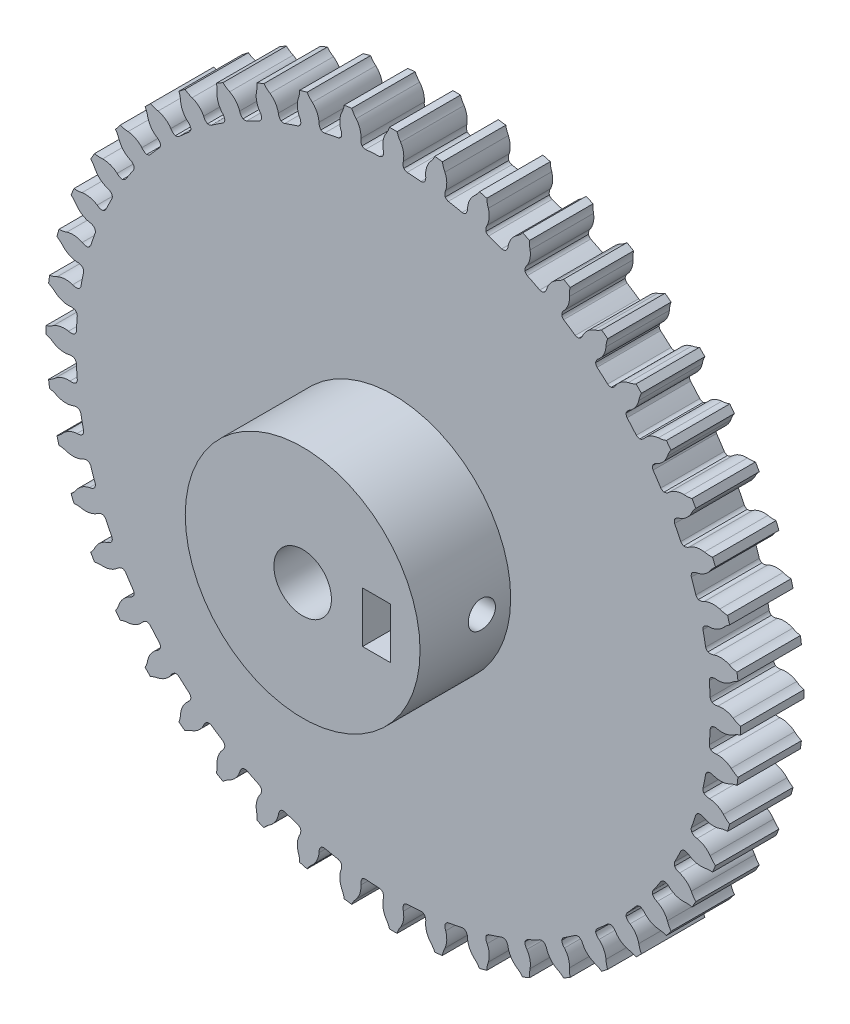
SolidWorks part; units mm, degrees
ref_plane "Front Plane" through (0, 0, 0) normal (0, 0, 1) x (1, 0, 0)
ref_plane "Top Plane" through (0, 0, 0) normal (0, 1, 0) x (1, 0, 0)
ref_plane "Right Plane" through (0, 0, 0) normal (1, 0, 0) x (0, 0, -1)
sketch "Sketch1" plane through (0, 0, 0) normal (0, 0, 1) x (1, 0, 0)
  line L0 (27.683, 56.4388) -> (28.5235, 56.4388)
  line L1 (28.5235, 56.4388) -> (28.1033, 56.4388)
  line L2 (32.6869, 56.1659) -> (33.5201, 56.0562)
  line L3 (33.5201, 56.0562) -> (33.1035, 56.1111)
  line L4 (37.6123, 55.2422) -> (38.4241, 55.0247)
  line L5 (38.4241, 55.0247) -> (38.0182, 55.1335)
  line L6 (42.375, 53.6836) -> (43.1514, 53.3619)
  line L7 (43.1514, 53.3619) -> (42.7632, 53.5227)
  line L8 (46.8935, 51.5166) -> (47.6213, 51.0964)
  line L9 (47.6213, 51.0964) -> (47.2574, 51.3065)
  line L10 (51.0905, 48.7783) -> (51.7572, 48.2667)
  line L11 (51.7572, 48.2667) -> (51.4239, 48.5225)
  line L12 (54.8942, 45.5157) -> (55.4884, 44.9214)
  line L13 (55.4884, 44.9214) -> (55.1913, 45.2186)
  line L14 (58.2394, 41.7845) -> (58.7511, 41.1177)
  line L15 (58.7511, 41.1177) -> (58.4953, 41.4511)
  line L16 (61.0691, 37.6486) -> (61.4893, 36.9207)
  line L17 (61.4893, 36.9207) -> (61.2792, 37.2847)
  line L18 (63.3347, 33.1787) -> (63.6563, 32.4022)
  line L19 (63.6563, 32.4022) -> (63.4955, 32.7905)
  line L20 (64.9974, 28.4513) -> (65.215, 27.6395)
  line L21 (65.215, 27.6395) -> (65.1062, 28.0454)
  line L22 (66.0289, 23.5474) -> (66.1386, 22.7141)
  line L23 (66.1386, 22.7141) -> (66.0838, 23.1308)
  line L24 (66.4115, 18.5507) -> (66.4115, 17.7103)
  line L25 (66.4115, 17.7103) -> (66.4115, 18.1305)
  line L26 (66.1386, 13.5469) -> (66.0289, 12.7137)
  line L27 (66.0289, 12.7137) -> (66.0838, 13.1303)
  line L28 (65.215, 8.6215) -> (64.9974, 7.8097)
  line L29 (64.9974, 7.8097) -> (65.1062, 8.2156)
  line L30 (63.6563, 3.8588) -> (63.3347, 3.0824)
  line L31 (63.3347, 3.0824) -> (63.4955, 3.4706)
  line L32 (61.4893, -0.6597) -> (61.0691, -1.3875)
  line L33 (61.0691, -1.3875) -> (61.2792, -1.0236)
  line L34 (58.7511, -4.8567) -> (58.2394, -5.5235)
  line L35 (58.2394, -5.5235) -> (58.4953, -5.1901)
  line L36 (55.4884, -8.6604) -> (54.8942, -9.2546)
  line L37 (54.8942, -9.2546) -> (55.1913, -8.9575)
  line L38 (51.7572, -12.0057) -> (51.0905, -12.5173)
  line L39 (51.0905, -12.5173) -> (51.4239, -12.2615)
  line L40 (47.6213, -14.8353) -> (46.8935, -15.2555)
  line L41 (46.8935, -15.2555) -> (47.2574, -15.0454)
  line L42 (43.1514, -17.1009) -> (42.375, -17.4225)
  line L43 (42.375, -17.4225) -> (42.7632, -17.2617)
  line L44 (38.4241, -18.7637) -> (37.6123, -18.9812)
  line L45 (37.6123, -18.9812) -> (38.0182, -18.8724)
  line L46 (33.5201, -19.7952) -> (32.6869, -19.9049)
  line L47 (32.6869, -19.9049) -> (33.1035, -19.85)
  line L48 (28.5235, -20.1777) -> (27.683, -20.1777)
  line L49 (27.683, -20.1777) -> (28.1033, -20.1777)
  line L50 (23.5196, -19.9049) -> (22.6864, -19.7952)
  line L51 (22.6864, -19.7952) -> (23.103, -19.85)
  line L52 (18.5942, -18.9812) -> (17.7825, -18.7637)
  line L53 (17.7825, -18.7637) -> (18.1883, -18.8724)
  line L54 (13.8315, -17.4225) -> (13.0551, -17.1009)
  line L55 (13.0551, -17.1009) -> (13.4433, -17.2617)
  line L56 (9.313, -15.2555) -> (8.5852, -14.8353)
  line L57 (8.5852, -14.8353) -> (8.9491, -15.0454)
  line L58 (5.116, -12.5173) -> (4.4493, -12.0057)
  line L59 (4.4493, -12.0057) -> (4.7827, -12.2615)
  line L60 (1.3124, -9.2546) -> (0.7181, -8.6604)
  line L61 (0.7181, -8.6604) -> (1.0152, -8.9575)
  line L62 (-2.0329, -5.5235) -> (-2.5445, -4.8567)
  line L63 (-2.5445, -4.8567) -> (-2.2887, -5.1901)
  line L64 (-4.8626, -1.3875) -> (-5.2828, -0.6597)
  line L65 (-5.2828, -0.6597) -> (-5.0727, -1.0236)
  line L66 (-7.1282, 3.0824) -> (-7.4498, 3.8588)
  line L67 (-7.4498, 3.8588) -> (-7.289, 3.4706)
  line L68 (-8.7909, 7.8097) -> (-9.0084, 8.6215)
  line L69 (-9.0084, 8.6215) -> (-8.8997, 8.2156)
  line L70 (-9.8224, 12.7137) -> (-9.9321, 13.5469)
  line L71 (-9.9321, 13.5469) -> (-9.8773, 13.1303)
  line L72 (-10.205, 17.7103) -> (-10.205, 18.5507)
  line L73 (-10.205, 18.5507) -> (-10.205, 18.1305)
  line L74 (-9.9321, 22.7141) -> (-9.8224, 23.5474)
  line L75 (-9.8224, 23.5474) -> (-9.8773, 23.1308)
  line L76 (-9.0084, 27.6395) -> (-8.7909, 28.4513)
  line L77 (-8.7909, 28.4513) -> (-8.8997, 28.0454)
  line L78 (-7.4498, 32.4022) -> (-7.1282, 33.1787)
  line L79 (-7.1282, 33.1787) -> (-7.289, 32.7905)
  line L80 (-5.2828, 36.9207) -> (-4.8626, 37.6486)
  line L81 (-4.8626, 37.6486) -> (-5.0727, 37.2847)
  line L82 (-2.5445, 41.1177) -> (-2.0329, 41.7845)
  line L83 (-2.0329, 41.7845) -> (-2.2887, 41.4511)
  line L84 (0.7181, 44.9214) -> (1.3124, 45.5157)
  line L85 (1.3124, 45.5157) -> (1.0152, 45.2186)
  line L86 (4.4493, 48.2667) -> (5.116, 48.7783)
  line L87 (5.116, 48.7783) -> (4.7827, 48.5225)
  line L88 (8.5852, 51.0964) -> (9.313, 51.5166)
  line L89 (9.313, 51.5166) -> (8.9491, 51.3065)
  line L90 (13.0551, 53.3619) -> (13.8315, 53.6836)
  line L91 (13.8315, 53.6836) -> (13.4433, 53.5227)
  line L92 (17.7825, 55.0247) -> (18.5942, 55.2422)
  line L93 (18.5942, 55.2422) -> (18.1883, 55.1335)
  line L94 (22.6864, 56.0562) -> (23.5196, 56.1659)
  line L95 (23.5196, 56.1659) -> (23.103, 56.1111)
  circle A1 centre (28.1033, 18.1305) radius 3.175
  circle A2 centre (28.1033, 18.1305) radius 12.9562
  arc A3 (28.5235, 56.4388) -> (28.9112, 55.6351) centre (31.0099, 57.143) ccw
  arc A4 (28.9112, 55.6351) -> (29.2209, 53.961) centre (26.9235, 54.4016) cw
  arc A5 (29.2209, 53.961) -> (29.2628, 53.2997) centre (30.05, 53.6815) ccw
  arc A7 (33.5201, 56.0562) -> (33.7996, 55.2088) centre (36.0771, 56.4298) ccw
  arc A9 (26.9856, 53.961) -> (26.9437, 53.2997) centre (26.1566, 53.6815) cw
  arc A10 (27.2953, 55.6351) -> (26.9856, 53.961) centre (29.2831, 54.4016) ccw
  arc A11 (27.683, 56.4388) -> (27.2953, 55.6351) centre (25.1967, 57.143) cw
  arc A12 (26.9437, 53.2997) -> (26.5846, 53.0976) centre (26.4555, 53.7469) cw
  arc A13 (29.2628, 53.2997) -> (29.6219, 53.0976) centre (29.751, 53.7469) ccw
  arc A14 (33.7996, 55.2088) -> (33.8882, 53.5085) centre (31.6679, 54.2453) cw
  arc A15 (33.8882, 53.5085) -> (33.8434, 52.8474) centre (34.6736, 53.1233) ccw
  arc A16 (31.6719, 53.8003) -> (31.5441, 53.1501) centre (30.8135, 53.6314) cw
  arc A17 (32.1975, 55.4197) -> (31.6719, 53.8003) centre (34.0073, 53.9373) ccw
  arc A18 (32.6869, 56.1659) -> (32.1975, 55.4197) centre (30.3137, 57.1886) cw
  arc A19 (31.5441, 53.1501) -> (31.1617, 52.9966) centre (31.1185, 53.6573) cw
  arc A20 (33.8434, 52.8474) -> (34.173, 52.6002) centre (34.3858, 53.2271) ccw
  arc A21 (38.4241, 55.0247) -> (38.5906, 54.148) centre (41.008, 55.0614) ccw
  arc A22 (38.5906, 54.148) -> (38.4565, 52.4508) centre (36.3513, 53.4711) cw
  arc A23 (38.4565, 52.4508) -> (38.3258, 51.8012) centre (39.1849, 51.9663) ccw
  arc A24 (36.2973, 53.0293) -> (36.0856, 52.4014) centre (35.4242, 52.974) cw
  arc A25 (37.0297, 54.5663) -> (36.2973, 53.0293) centre (38.6305, 52.8604) ccw
  arc A26 (37.6123, 55.2422) -> (37.0297, 54.5663) centre (35.3929, 56.5659) cw
  arc A27 (36.0856, 52.4014) -> (35.6865, 52.2991) centre (35.7299, 52.9598) cw
  arc A28 (38.3258, 51.8012) -> (38.6203, 51.513) centre (38.913, 52.1069) ccw
  arc A29 (43.1514, 53.3619) -> (43.2021, 52.471) centre (45.718, 53.061) ccw
  arc A30 (43.2021, 52.471) -> (42.8476, 50.8058) centre (40.8936, 52.0921) cw
  arc A31 (42.8476, 50.8058) -> (42.6332, 50.1788) centre (43.5065, 50.2304) ccw
  arc A32 (40.7824, 51.6612) -> (40.4906, 51.0663) centre (39.9095, 51.7203) cw
  arc A33 (41.7092, 53.0894) -> (40.7824, 51.6612) centre (43.0736, 51.1892) ccw
  arc A34 (42.375, 53.6836) -> (41.7092, 53.0894) centre (40.3473, 55.2856) cw
  arc A35 (40.4906, 51.0663) -> (40.0815, 51.017) centre (40.2108, 51.6663) cw
  arc A36 (42.6332, 50.1788) -> (42.8876, 49.8547) centre (43.2554, 50.4052) ccw
  arc A37 (47.6213, 51.0964) -> (47.5553, 50.2064) centre (50.1267, 50.463) ccw
  arc A38 (47.5553, 50.2064) -> (46.9864, 48.6017) centre (45.2171, 50.1321) cw
  arc A39 (46.9864, 48.6017) -> (46.692, 48.0081) centre (47.5646, 47.9452) ccw
  arc A40 (45.0505, 49.7194) -> (44.6836, 49.1677) centre (44.1928, 49.8919) cw
  arc A41 (46.1558, 51.0144) -> (45.0505, 49.7194) centre (47.2606, 48.9523) ccw
  arc A42 (46.8935, 51.5166) -> (46.1558, 51.0144) centre (45.0923, 53.3696) cw
  arc A43 (44.6836, 49.1677) -> (44.2716, 49.1722) centre (44.4845, 49.7991) cw
  arc A44 (46.692, 48.0081) -> (46.902, 47.6535) centre (47.3384, 48.1514) ccw
  arc A45 (51.7572, 48.2667) -> (51.5756, 47.393) centre (54.1585, 47.3118) ccw
  arc A46 (51.5756, 47.393) -> (50.8022, 45.8763) centre (49.2477, 47.6245) cw
  arc A47 (50.8022, 45.8763) -> (50.4328, 45.3262) centre (51.2897, 45.1499) ccw
  arc A48 (49.0287, 47.2371) -> (48.5929, 46.738) centre (48.2009, 47.5201) cw
  arc A49 (50.2936, 48.3767) -> (49.0287, 47.2371) centre (51.1197, 46.1881) ccw
  arc A50 (51.0905, 48.7783) -> (50.2936, 48.3767) centre (49.5466, 50.8506) cw
  arc A51 (48.5929, 46.738) -> (48.185, 46.7962) centre (48.4779, 47.39) cw
  arc A52 (50.4328, 45.3262) -> (50.5947, 44.9472) centre (51.0924, 45.3838) ccw
  arc A53 (55.4884, 44.9214) -> (55.1943, 44.0789) centre (57.7445, 43.6612) ccw
  arc A54 (55.1943, 44.0789) -> (54.2295, 42.6761) centre (52.9166, 44.6123) cw
  arc A55 (54.2295, 42.6761) -> (53.7915, 42.1789) centre (54.6181, 41.8923) ccw
  arc A56 (52.6489, 44.2568) -> (52.1517, 43.8188) centre (51.8651, 44.6454) cw
  arc A57 (54.0517, 45.2216) -> (52.6489, 44.2568) centre (54.5851, 42.9438) ccw
  arc A58 (54.8942, 45.5157) -> (54.0517, 45.2216) centre (53.634, 47.7718) cw
  arc A59 (52.1517, 43.8188) -> (51.7548, 43.9298) centre (52.1227, 44.4802) cw
  arc A60 (53.7915, 42.1789) -> (53.9025, 41.7821) centre (54.453, 42.15) ccw
  arc A61 (58.7511, 41.1177) -> (58.3495, 40.3208) centre (60.8233, 39.5738) ccw
  arc A62 (58.3495, 40.3208) -> (57.2099, 39.056) centre (56.1608, 41.147) cw
  arc A63 (57.2099, 39.056) -> (56.7107, 38.6202) centre (57.4928, 38.2282) ccw
  arc A64 (55.849, 40.8294) -> (55.2989, 40.4601) centre (55.1227, 41.317) cw
  arc A65 (57.3658, 41.6029) -> (55.849, 40.8294) centre (57.5973, 39.275) ccw
  arc A66 (58.2394, 41.7845) -> (57.3658, 41.6029) centre (57.2845, 44.1858) cw
  arc A67 (55.2989, 40.4601) -> (54.92, 40.6219) centre (55.3566, 41.1196) cw
  arc A68 (56.7107, 38.6202) -> (56.769, 38.2123) centre (57.3627, 38.5052) ccw
  arc A69 (61.4893, 36.9207) -> (60.9871, 36.1831) centre (63.3423, 35.1196) ccw
  arc A70 (60.9871, 36.1831) -> (59.6922, 35.0778) centre (58.9251, 37.2878) cw
  arc A71 (59.6922, 35.0778) -> (59.1404, 34.7109) centre (59.8647, 34.2201) ccw
  arc A72 (58.5745, 37.0137) -> (57.9809, 36.7193) centre (57.9179, 37.5919) cw
  arc A73 (60.1792, 37.5825) -> (58.5745, 37.0137) centre (60.1049, 35.2443) ccw
  arc A74 (61.0691, 37.6486) -> (60.1792, 37.5825) centre (60.4357, 40.1539) cw
  arc A75 (57.9809, 36.7193) -> (57.6263, 36.9292) centre (58.1241, 37.3657) cw
  arc A76 (59.1404, 34.7109) -> (59.1449, 34.2988) centre (59.7718, 34.5118) ccw
  arc A77 (63.6563, 32.4022) -> (63.0621, 31.7364) centre (65.2584, 30.3746) ccw
  arc A78 (63.0621, 31.7364) -> (61.634, 30.8096) centre (61.1619, 33.1009) cw
  arc A79 (61.634, 30.8096) -> (61.0391, 30.5179) centre (61.693, 29.9368) ccw
  arc A80 (60.7785, 32.8748) -> (60.1516, 32.6605) centre (60.2031, 33.5338) cw
  arc A81 (62.4438, 33.2294) -> (60.7785, 32.8748) centre (62.0649, 30.9209) ccw
  arc A82 (63.3347, 33.1787) -> (62.4438, 33.2294) centre (63.0338, 35.7453) cw
  arc A83 (60.1516, 32.6605) -> (59.8274, 32.9149) centre (60.378, 33.2826) cw
  arc A84 (61.0391, 30.5179) -> (60.9898, 30.1088) centre (61.6391, 30.238) ccw
  arc A85 (65.215, 27.6395) -> (64.539, 27.057) centre (66.5387, 25.4201) ccw
  arc A86 (64.539, 27.057) -> (63.0021, 26.3245) centre (62.8331, 28.6578) cw
  arc A87 (63.0021, 26.3245) -> (62.3742, 26.1129) centre (62.9467, 25.4514) ccw
  arc A88 (62.4235, 28.4837) -> (61.7739, 28.353) centre (61.939, 29.2122) cw
  arc A89 (64.1208, 28.6179) -> (62.4235, 28.4837) centre (63.4438, 26.3786) ccw
  arc A90 (64.9974, 28.4513) -> (64.1208, 28.6179) centre (65.0341, 31.0352) cw
  arc A91 (61.7739, 28.353) -> (61.4858, 28.6476) centre (62.0796, 28.9403) cw
  arc A92 (62.3742, 26.1129) -> (62.2719, 25.7137) centre (62.9325, 25.7571) ccw
  arc A93 (66.1386, 22.7141) -> (65.3924, 22.2248) centre (67.1613, 20.3409) ccw
  arc A94 (65.3924, 22.2248) -> (63.773, 21.6992) centre (63.9101, 24.0346) cw
  arc A95 (63.773, 21.6992) -> (63.1229, 21.5714) centre (63.6042, 20.8408) ccw
  arc A96 (63.4813, 23.9155) -> (62.8202, 23.8707) centre (63.096, 24.7009) cw
  arc A97 (65.1815, 23.8269) -> (63.4813, 23.9155) centre (64.2181, 21.6951) ccw
  arc A98 (66.0289, 23.5474) -> (65.1815, 23.8269) centre (66.4026, 26.1044) cw
  arc A99 (62.8202, 23.8707) -> (62.5729, 24.2003) centre (63.1999, 24.413) cw
  arc A100 (63.1229, 21.5714) -> (62.9694, 21.189) centre (63.63, 21.1458) ccw
  arc A101 (66.4115, 17.7103) -> (65.6078, 17.3225) centre (67.1157, 15.2239) ccw
  arc A102 (65.6078, 17.3225) -> (63.9337, 17.0128) centre (64.3744, 19.3103) cw
  arc A103 (63.9337, 17.0128) -> (63.2724, 16.971) centre (63.6542, 16.1838) ccw
  arc A104 (63.9337, 19.2482) -> (63.2724, 19.2901) centre (63.6542, 20.0772) cw
  arc A105 (65.6078, 18.9385) -> (63.9337, 19.2482) centre (64.3744, 16.9507) ccw
  arc A106 (66.4115, 18.5507) -> (65.6078, 18.9385) centre (67.1157, 21.0371) cw
  arc A107 (63.2724, 19.2901) -> (63.0703, 19.6492) centre (63.7197, 19.7782) cw
  arc A108 (63.2724, 16.971) -> (63.0703, 16.6119) centre (63.7197, 16.4828) ccw
  arc A109 (66.0289, 12.7137) -> (65.1815, 12.4341) centre (66.4026, 10.1566) ccw
  arc A110 (65.1815, 12.4341) -> (63.4813, 12.3456) centre (64.2181, 14.5659) cw
  arc A111 (63.4813, 12.3456) -> (62.8202, 12.3904) centre (63.096, 11.5601) ccw
  arc A112 (63.773, 14.5618) -> (63.1229, 14.6897) centre (63.6042, 15.4202) cw
  arc A113 (65.3924, 14.0363) -> (63.773, 14.5618) centre (63.9101, 12.2265) ccw
  arc A114 (66.1386, 13.5469) -> (65.3924, 14.0363) centre (67.1613, 15.9201) cw
  arc A115 (63.1229, 14.6897) -> (62.9694, 15.0721) centre (63.63, 15.1153) cw
  arc A116 (62.8202, 12.3904) -> (62.5729, 12.0607) centre (63.1999, 11.848) ccw
  arc A117 (64.9974, 7.8097) -> (64.1208, 7.6432) centre (65.0341, 5.2258) ccw
  arc A118 (64.1208, 7.6432) -> (62.4235, 7.7773) centre (63.4438, 9.8825) cw
  arc A119 (62.4235, 7.7773) -> (61.7739, 7.908) centre (61.939, 7.0489) ccw
  arc A120 (63.0021, 9.9365) -> (62.3742, 10.1481) centre (62.9467, 10.8096) cw
  arc A121 (64.539, 9.2041) -> (63.0021, 9.9365) centre (62.8331, 7.6033) ccw
  arc A122 (65.215, 8.6215) -> (64.539, 9.2041) centre (66.5387, 10.8409) cw
  arc A123 (62.3742, 10.1481) -> (62.2719, 10.5473) centre (62.9325, 10.5039) cw
  arc A124 (61.7739, 7.908) -> (61.4858, 7.6135) centre (62.0796, 7.3207) ccw
  arc A125 (63.3347, 3.0824) -> (62.4438, 3.0317) centre (63.0338, 0.5158) ccw
  arc A126 (62.4438, 3.0317) -> (60.7785, 3.3862) centre (62.0649, 5.3402) cw
  arc A127 (60.7785, 3.3862) -> (60.1516, 3.6006) centre (60.2031, 2.7272) ccw
  arc A128 (61.634, 5.4514) -> (61.0391, 5.7432) centre (61.693, 6.3243) cw
  arc A129 (63.0621, 4.5246) -> (61.634, 5.4514) centre (61.1619, 3.1602) ccw
  arc A130 (63.6563, 3.8588) -> (63.0621, 4.5246) centre (65.2584, 5.8864) cw
  arc A131 (61.0391, 5.7432) -> (60.9898, 6.1523) centre (61.6391, 6.023) cw
  arc A132 (60.1516, 3.6006) -> (59.8274, 3.3462) centre (60.378, 2.9784) ccw
  arc A133 (61.0691, -1.3875) -> (60.1792, -1.3215) centre (60.4357, -3.8929) ccw
  arc A134 (60.1792, -1.3215) -> (58.5745, -0.7526) centre (60.1049, 1.0167) cw
  arc A135 (58.5745, -0.7526) -> (57.9809, -0.4583) centre (57.9179, -1.3309) ccw
  arc A136 (59.6922, 1.1833) -> (59.1404, 1.5502) centre (59.8647, 2.0409) cw
  arc A137 (60.9871, 0.078) -> (59.6922, 1.1833) centre (58.9251, -1.0268) ccw
  arc A138 (61.4893, -0.6597) -> (60.9871, 0.078) centre (63.3423, 1.1415) cw
  arc A139 (59.1404, 1.5502) -> (59.1449, 1.9622) centre (59.7718, 1.7493) cw
  arc A140 (57.9809, -0.4583) -> (57.6263, -0.6682) centre (58.1241, -1.1046) ccw
  arc A141 (58.2394, -5.5235) -> (57.3658, -5.3418) centre (57.2845, -7.9247) ccw
  arc A142 (57.3658, -5.3418) -> (55.849, -4.5684) centre (57.5973, -3.0139) cw
  arc A143 (55.849, -4.5684) -> (55.2989, -4.199) centre (55.1227, -5.056) ccw
  arc A144 (57.2099, -2.7949) -> (56.7107, -2.3592) centre (57.4928, -1.9671) cw
  arc A145 (58.3495, -4.0598) -> (57.2099, -2.7949) centre (56.1608, -4.8859) ccw
  arc A146 (58.7511, -4.8567) -> (58.3495, -4.0598) centre (60.8233, -3.3128) cw
  arc A147 (56.7107, -2.3592) -> (56.769, -1.9512) centre (57.3627, -2.2441) cw
  arc A148 (55.2989, -4.199) -> (54.92, -4.3609) centre (55.3566, -4.8586) ccw
  arc A149 (54.8942, -9.2546) -> (54.0517, -8.9605) centre (53.634, -11.5107) ccw
  arc A150 (54.0517, -8.9605) -> (52.6489, -7.9957) centre (54.5851, -6.6828) cw
  arc A151 (52.6489, -7.9957) -> (52.1517, -7.5578) centre (51.8651, -8.3843) ccw
  arc A152 (54.2295, -6.4151) -> (53.7915, -5.9179) centre (54.6181, -5.6313) cw
  arc A153 (55.1943, -7.8179) -> (54.2295, -6.4151) centre (52.9166, -8.3513) ccw
  arc A154 (55.4884, -8.6604) -> (55.1943, -7.8179) centre (57.7445, -7.4002) cw
  arc A155 (53.7915, -5.9179) -> (53.9025, -5.5211) centre (54.453, -5.889) cw
  arc A156 (52.1517, -7.5578) -> (51.7548, -7.6688) centre (52.1227, -8.2192) ccw
  arc A157 (51.0905, -12.5173) -> (50.2936, -12.1157) centre (49.5466, -14.5896) ccw
  arc A158 (50.2936, -12.1157) -> (49.0287, -10.9761) centre (51.1197, -9.9271) cw
  arc A159 (49.0287, -10.9761) -> (48.5929, -10.4769) centre (48.2009, -11.259) ccw
  arc A160 (50.8022, -9.6153) -> (50.4328, -9.0651) centre (51.2897, -8.8889) cw
  arc A161 (51.5756, -11.132) -> (50.8022, -9.6153) centre (49.2477, -11.3635) ccw
  arc A162 (51.7572, -12.0057) -> (51.5756, -11.132) centre (54.1585, -11.0507) cw
  arc A163 (50.4328, -9.0651) -> (50.5947, -8.6862) centre (51.0924, -9.1228) cw
  arc A164 (48.5929, -10.4769) -> (48.185, -10.5352) centre (48.4779, -11.1289) ccw
  arc A165 (46.8935, -15.2555) -> (46.1558, -14.7534) centre (45.0923, -17.1086) ccw
  arc A166 (46.1558, -14.7534) -> (45.0505, -13.4584) centre (47.2606, -12.6913) cw
  arc A167 (45.0505, -13.4584) -> (44.6836, -12.9066) centre (44.1928, -13.6309) ccw
  arc A168 (46.9864, -12.3407) -> (46.692, -11.7471) centre (47.5646, -11.6842) cw
  arc A169 (47.5553, -13.9454) -> (46.9864, -12.3407) centre (45.2171, -13.8711) ccw
  arc A170 (47.6213, -14.8353) -> (47.5553, -13.9454) centre (50.1267, -14.202) cw
  arc A171 (46.692, -11.7471) -> (46.902, -11.3925) centre (47.3384, -11.8903) cw
  arc A172 (44.6836, -12.9066) -> (44.2716, -12.9111) centre (44.4845, -13.538) ccw
  arc A173 (42.375, -17.4225) -> (41.7092, -16.8284) centre (40.3473, -19.0246) ccw
  arc A174 (41.7092, -16.8284) -> (40.7824, -15.4002) centre (43.0736, -14.9281) cw
  arc A175 (40.7824, -15.4002) -> (40.4906, -14.8053) centre (39.9095, -15.4593) ccw
  arc A176 (42.8476, -14.5448) -> (42.6332, -13.9178) centre (43.5065, -13.9693) cw
  arc A177 (43.2021, -16.21) -> (42.8476, -14.5448) centre (40.8936, -15.8311) ccw
  arc A178 (43.1514, -17.1009) -> (43.2021, -16.21) centre (45.718, -16.8) cw
  arc A179 (42.6332, -13.9178) -> (42.8876, -13.5936) centre (43.2554, -14.1442) cw
  arc A180 (40.4906, -14.8053) -> (40.0815, -14.756) centre (40.2108, -15.4053) ccw
  arc A181 (37.6123, -18.9812) -> (37.0297, -18.3052) centre (35.3929, -20.3049) ccw
  arc A182 (37.0297, -18.3052) -> (36.2973, -16.7683) centre (38.6305, -16.5993) cw
  arc A183 (36.2973, -16.7683) -> (36.0856, -16.1404) centre (35.4242, -16.7129) ccw
  arc A184 (38.4565, -16.1897) -> (38.3258, -15.5401) centre (39.1849, -15.7052) cw
  arc A185 (38.5906, -17.887) -> (38.4565, -16.1897) centre (36.3513, -17.21) ccw
  arc A186 (38.4241, -18.7637) -> (38.5906, -17.887) centre (41.008, -18.8003) cw
  arc A187 (38.3258, -15.5401) -> (38.6203, -15.252) centre (38.913, -15.8458) cw
  arc A188 (36.0856, -16.1404) -> (35.6865, -16.0381) centre (35.7299, -16.6987) ccw
  arc A189 (32.6869, -19.9049) -> (32.1975, -19.1586) centre (30.3137, -20.9276) ccw
  arc A190 (32.1975, -19.1586) -> (31.6719, -17.5393) centre (34.0073, -17.6763) cw
  arc A191 (31.6719, -17.5393) -> (31.5441, -16.8891) centre (30.8135, -17.3704) ccw
  arc A192 (33.8882, -17.2475) -> (33.8434, -16.5864) centre (34.6736, -16.8622) cw
  arc A193 (33.7996, -18.9477) -> (33.8882, -17.2475) centre (31.6679, -17.9843) ccw
  arc A194 (33.5201, -19.7952) -> (33.7996, -18.9477) centre (36.0771, -20.1688) cw
  arc A195 (33.8434, -16.5864) -> (34.173, -16.3391) centre (34.3858, -16.9661) cw
  arc A196 (31.5441, -16.8891) -> (31.1617, -16.7356) centre (31.1185, -17.3962) ccw
  arc A197 (27.683, -20.1777) -> (27.2953, -19.374) centre (25.1967, -20.8819) ccw
  arc A198 (27.2953, -19.374) -> (26.9856, -17.6999) centre (29.2831, -18.1406) cw
  arc A199 (26.9856, -17.6999) -> (26.9437, -17.0386) centre (26.1566, -17.4204) ccw
  arc A200 (29.2209, -17.6999) -> (29.2628, -17.0386) centre (30.05, -17.4204) cw
  arc A201 (28.9112, -19.374) -> (29.2209, -17.6999) centre (26.9235, -18.1406) ccw
  arc A202 (28.5235, -20.1777) -> (28.9112, -19.374) centre (31.0099, -20.8819) cw
  arc A203 (29.2628, -17.0386) -> (29.6219, -16.8365) centre (29.751, -17.4859) cw
  arc A204 (26.9437, -17.0386) -> (26.5846, -16.8365) centre (26.4555, -17.4859) ccw
  arc A205 (22.6864, -19.7952) -> (22.4069, -18.9477) centre (20.1294, -20.1688) ccw
  arc A206 (22.4069, -18.9477) -> (22.3183, -17.2475) centre (24.5386, -17.9843) cw
  arc A207 (22.3183, -17.2475) -> (22.3631, -16.5864) centre (21.5329, -16.8622) ccw
  arc A208 (24.5346, -17.5393) -> (24.6624, -16.8891) centre (25.393, -17.3704) cw
  arc A209 (24.009, -19.1586) -> (24.5346, -17.5393) centre (22.1992, -17.6763) ccw
  arc A210 (23.5196, -19.9049) -> (24.009, -19.1586) centre (25.8928, -20.9276) cw
  arc A211 (24.6624, -16.8891) -> (25.0448, -16.7356) centre (25.088, -17.3962) cw
  arc A212 (22.3631, -16.5864) -> (22.0335, -16.3391) centre (21.8208, -16.9661) ccw
  arc A213 (17.7825, -18.7637) -> (17.6159, -17.887) centre (15.1985, -18.8003) ccw
  arc A214 (17.6159, -17.887) -> (17.7501, -16.1897) centre (19.8552, -17.21) cw
  arc A215 (17.7501, -16.1897) -> (17.8808, -15.5401) centre (17.0216, -15.7052) ccw
  arc A216 (19.9093, -16.7683) -> (20.1209, -16.1404) centre (20.7824, -16.7129) cw
  arc A217 (19.1768, -18.3052) -> (19.9093, -16.7683) centre (17.576, -16.5993) ccw
  arc A218 (18.5942, -18.9812) -> (19.1768, -18.3052) centre (20.8136, -20.3049) cw
  arc A219 (20.1209, -16.1404) -> (20.52, -16.0381) centre (20.4766, -16.6987) cw
  arc A220 (17.8808, -15.5401) -> (17.5862, -15.252) centre (17.2935, -15.8458) ccw
  arc A221 (13.0551, -17.1009) -> (13.0044, -16.21) centre (10.4885, -16.8) ccw
  arc A222 (13.0044, -16.21) -> (13.3589, -14.5448) centre (15.3129, -15.8311) cw
  arc A223 (13.3589, -14.5448) -> (13.5733, -13.9178) centre (12.7, -13.9693) ccw
  arc A224 (15.4242, -15.4002) -> (15.7159, -14.8053) centre (16.297, -15.4593) cw
  arc A225 (14.4974, -16.8284) -> (15.4242, -15.4002) centre (13.1329, -14.9281) ccw
  arc A226 (13.8315, -17.4225) -> (14.4974, -16.8284) centre (15.8592, -19.0246) cw
  arc A227 (15.7159, -14.8053) -> (16.125, -14.756) centre (15.9957, -15.4053) cw
  arc A228 (13.5733, -13.9178) -> (13.3189, -13.5936) centre (12.9512, -14.1442) ccw
  arc A229 (8.5852, -14.8353) -> (8.6513, -13.9454) centre (6.0798, -14.202) ccw
  arc A230 (8.6513, -13.9454) -> (9.2201, -12.3407) centre (10.9894, -13.8711) cw
  arc A231 (9.2201, -12.3407) -> (9.5145, -11.7471) centre (8.6419, -11.6842) ccw
  arc A232 (11.156, -13.4584) -> (11.5229, -12.9066) centre (12.0137, -13.6309) cw
  arc A233 (10.0507, -14.7534) -> (11.156, -13.4584) centre (8.946, -12.6913) ccw
  arc A234 (9.313, -15.2555) -> (10.0507, -14.7534) centre (11.1142, -17.1086) cw
  arc A235 (11.5229, -12.9066) -> (11.9349, -12.9111) centre (11.722, -13.538) cw
  arc A236 (9.5145, -11.7471) -> (9.3045, -11.3925) centre (8.8681, -11.8903) ccw
  arc A237 (4.4493, -12.0057) -> (4.6309, -11.132) centre (2.048, -11.0507) ccw
  arc A238 (4.6309, -11.132) -> (5.4044, -9.6153) centre (6.9588, -11.3635) cw
  arc A239 (5.4044, -9.6153) -> (5.7737, -9.0651) centre (4.9168, -8.8889) ccw
  arc A240 (7.1778, -10.9761) -> (7.6136, -10.4769) centre (8.0056, -11.259) cw
  arc A241 (5.9129, -12.1157) -> (7.1778, -10.9761) centre (5.0868, -9.9271) ccw
  arc A242 (5.116, -12.5173) -> (5.9129, -12.1157) centre (6.6599, -14.5896) cw
  arc A243 (7.6136, -10.4769) -> (8.0215, -10.5352) centre (7.7286, -11.1289) cw
  arc A244 (5.7737, -9.0651) -> (5.6118, -8.6862) centre (5.1141, -9.1228) ccw
  arc A245 (0.7181, -8.6604) -> (1.0122, -7.8179) centre (-1.538, -7.4002) ccw
  arc A246 (1.0122, -7.8179) -> (1.977, -6.4151) centre (3.29, -8.3513) cw
  arc A247 (1.977, -6.4151) -> (2.415, -5.9179) centre (1.5884, -5.6313) ccw
  arc A248 (3.5576, -7.9957) -> (4.0549, -7.5578) centre (4.3415, -8.3843) cw
  arc A249 (2.1549, -8.9605) -> (3.5576, -7.9957) centre (1.6215, -6.6828) ccw
  arc A250 (1.3124, -9.2546) -> (2.1549, -8.9605) centre (2.5726, -11.5107) cw
  arc A251 (4.0549, -7.5578) -> (4.4517, -7.6688) centre (4.0838, -8.2192) cw
  arc A252 (2.415, -5.9179) -> (2.304, -5.5211) centre (1.7535, -5.889) ccw
  arc A253 (-2.5445, -4.8567) -> (-2.143, -4.0598) centre (-4.6168, -3.3128) ccw
  arc A254 (-2.143, -4.0598) -> (-1.0033, -2.7949) centre (0.0457, -4.8859) cw
  arc A255 (-1.0033, -2.7949) -> (-0.5042, -2.3592) centre (-1.2863, -1.9671) ccw
  arc A256 (0.3575, -4.5684) -> (0.9076, -4.199) centre (1.0839, -5.056) cw
  arc A257 (-1.1592, -5.3418) -> (0.3575, -4.5684) centre (-1.3908, -3.0139) ccw
  arc A258 (-2.0329, -5.5235) -> (-1.1592, -5.3418) centre (-1.078, -7.9247) cw
  arc A259 (0.9076, -4.199) -> (1.2865, -4.3609) centre (0.8499, -4.8586) cw
  arc A260 (-0.5042, -2.3592) -> (-0.5625, -1.9512) centre (-1.1562, -2.2441) ccw
  arc A261 (-5.2828, -0.6597) -> (-4.7806, 0.078) centre (-7.1358, 1.1415) ccw
  arc A262 (-4.7806, 0.078) -> (-3.4856, 1.1833) centre (-2.7185, -1.0268) cw
  arc A263 (-3.4856, 1.1833) -> (-2.9339, 1.5502) centre (-3.6581, 2.0409) ccw
  arc A264 (-2.368, -0.7526) -> (-1.7743, -0.4583) centre (-1.7114, -1.3309) cw
  arc A265 (-3.9727, -1.3215) -> (-2.368, -0.7526) centre (-3.8983, 1.0167) ccw
  arc A266 (-4.8626, -1.3875) -> (-3.9727, -1.3215) centre (-4.2292, -3.8929) cw
  arc A267 (-1.7743, -0.4583) -> (-1.4198, -0.6682) centre (-1.9176, -1.1046) cw
  arc A268 (-2.9339, 1.5502) -> (-2.9384, 1.9622) centre (-3.5653, 1.7493) ccw
  arc A269 (-7.4498, 3.8588) -> (-6.8556, 4.5246) centre (-9.0519, 5.8864) ccw
  arc A270 (-6.8556, 4.5246) -> (-5.4275, 5.4514) centre (-4.9554, 3.1602) cw
  arc A271 (-5.4275, 5.4514) -> (-4.8325, 5.7432) centre (-5.4865, 6.3243) ccw
  arc A272 (-4.572, 3.3862) -> (-3.9451, 3.6006) centre (-3.9966, 2.7272) cw
  arc A273 (-6.2372, 3.0317) -> (-4.572, 3.3862) centre (-5.8584, 5.3402) ccw
  arc A274 (-7.1282, 3.0824) -> (-6.2372, 3.0317) centre (-6.8272, 0.5158) cw
  arc A275 (-3.9451, 3.6006) -> (-3.6209, 3.3462) centre (-4.1714, 2.9784) cw
  arc A276 (-4.8325, 5.7432) -> (-4.7832, 6.1523) centre (-5.4326, 6.023) ccw
  arc A277 (-9.0084, 8.6215) -> (-8.3325, 9.2041) centre (-10.3322, 10.8409) ccw
  arc A278 (-8.3325, 9.2041) -> (-6.7956, 9.9365) centre (-6.6266, 7.6033) cw
  arc A279 (-6.7956, 9.9365) -> (-6.1677, 10.1481) centre (-6.7402, 10.8096) ccw
  arc A280 (-6.217, 7.7773) -> (-5.5674, 7.908) centre (-5.7325, 7.0489) cw
  arc A281 (-7.9142, 7.6432) -> (-6.217, 7.7773) centre (-7.2373, 9.8825) ccw
  arc A282 (-8.7909, 7.8097) -> (-7.9142, 7.6432) centre (-8.8276, 5.2258) cw
  arc A283 (-5.5674, 7.908) -> (-5.2792, 7.6135) centre (-5.8731, 7.3207) cw
  arc A284 (-6.1677, 10.1481) -> (-6.0654, 10.5473) centre (-6.726, 10.5039) ccw
  arc A285 (-9.9321, 13.5469) -> (-9.1859, 14.0363) centre (-10.9548, 15.9201) ccw
  arc A286 (-9.1859, 14.0363) -> (-7.5665, 14.5618) centre (-7.7035, 12.2265) cw
  arc A287 (-7.5665, 14.5618) -> (-6.9164, 14.6897) centre (-7.3977, 15.4202) ccw
  arc A288 (-7.2748, 12.3456) -> (-6.6137, 12.3904) centre (-6.8895, 11.5601) cw
  arc A289 (-8.975, 12.4341) -> (-7.2748, 12.3456) centre (-8.0115, 14.5659) ccw
  arc A290 (-9.8224, 12.7137) -> (-8.975, 12.4341) centre (-10.1961, 10.1566) cw
  arc A291 (-6.6137, 12.3904) -> (-6.3664, 12.0607) centre (-6.9934, 11.848) cw
  arc A292 (-6.9164, 14.6897) -> (-6.7629, 15.0721) centre (-7.4235, 15.1153) ccw
  arc A293 (-10.205, 18.5507) -> (-9.4013, 18.9385) centre (-10.9092, 21.0371) ccw
  arc A294 (-9.4013, 18.9385) -> (-7.7272, 19.2482) centre (-8.1678, 16.9507) cw
  arc A295 (-7.7272, 19.2482) -> (-7.0659, 19.2901) centre (-7.4477, 20.0772) ccw
  arc A296 (-7.7272, 17.0128) -> (-7.0659, 16.971) centre (-7.4477, 16.1838) cw
  arc A297 (-9.4013, 17.3225) -> (-7.7272, 17.0128) centre (-8.1678, 19.3103) ccw
  arc A298 (-10.205, 17.7103) -> (-9.4013, 17.3225) centre (-10.9092, 15.2239) cw
  arc A299 (-7.0659, 16.971) -> (-6.8638, 16.6119) centre (-7.5131, 16.4828) cw
  arc A300 (-7.0659, 19.2901) -> (-6.8638, 19.6492) centre (-7.5131, 19.7782) ccw
  arc A301 (-9.8224, 23.5474) -> (-8.975, 23.8269) centre (-10.1961, 26.1044) ccw
  arc A302 (-8.975, 23.8269) -> (-7.2748, 23.9155) centre (-8.0115, 21.6951) cw
  arc A303 (-7.2748, 23.9155) -> (-6.6137, 23.8707) centre (-6.8895, 24.7009) ccw
  arc A304 (-7.5665, 21.6992) -> (-6.9164, 21.5714) centre (-7.3977, 20.8408) cw
  arc A305 (-9.1859, 22.2248) -> (-7.5665, 21.6992) centre (-7.7035, 24.0346) ccw
  arc A306 (-9.9321, 22.7141) -> (-9.1859, 22.2248) centre (-10.9548, 20.3409) cw
  arc A307 (-6.9164, 21.5714) -> (-6.7629, 21.189) centre (-7.4235, 21.1458) cw
  arc A308 (-6.6137, 23.8707) -> (-6.3664, 24.2003) centre (-6.9934, 24.413) ccw
  arc A309 (-8.7909, 28.4513) -> (-7.9142, 28.6179) centre (-8.8276, 31.0352) ccw
  arc A310 (-7.9142, 28.6179) -> (-6.217, 28.4837) centre (-7.2373, 26.3786) cw
  arc A311 (-6.217, 28.4837) -> (-5.5674, 28.353) centre (-5.7325, 29.2122) ccw
  arc A312 (-6.7956, 26.3245) -> (-6.1677, 26.1129) centre (-6.7402, 25.4514) cw
  arc A313 (-8.3325, 27.057) -> (-6.7956, 26.3245) centre (-6.6266, 28.6578) ccw
  arc A314 (-9.0084, 27.6395) -> (-8.3325, 27.057) centre (-10.3322, 25.4201) cw
  arc A315 (-6.1677, 26.1129) -> (-6.0654, 25.7137) centre (-6.726, 25.7571) cw
  arc A316 (-5.5674, 28.353) -> (-5.2792, 28.6476) centre (-5.8731, 28.9403) ccw
  arc A317 (-7.1282, 33.1787) -> (-6.2372, 33.2294) centre (-6.8272, 35.7453) ccw
  arc A318 (-6.2372, 33.2294) -> (-4.572, 32.8748) centre (-5.8584, 30.9209) cw
  arc A319 (-4.572, 32.8748) -> (-3.9451, 32.6605) centre (-3.9966, 33.5338) ccw
  arc A320 (-5.4275, 30.8096) -> (-4.8325, 30.5179) centre (-5.4865, 29.9368) cw
  arc A321 (-6.8556, 31.7364) -> (-5.4275, 30.8096) centre (-4.9554, 33.1009) ccw
  arc A322 (-7.4498, 32.4022) -> (-6.8556, 31.7364) centre (-9.0519, 30.3746) cw
  arc A323 (-4.8325, 30.5179) -> (-4.7832, 30.1088) centre (-5.4326, 30.238) cw
  arc A324 (-3.9451, 32.6605) -> (-3.6209, 32.9149) centre (-4.1714, 33.2826) ccw
  arc A325 (-4.8626, 37.6486) -> (-3.9727, 37.5825) centre (-4.2292, 40.1539) ccw
  arc A326 (-3.9727, 37.5825) -> (-2.368, 37.0137) centre (-3.8983, 35.2443) cw
  arc A327 (-2.368, 37.0137) -> (-1.7743, 36.7193) centre (-1.7114, 37.5919) ccw
  arc A328 (-3.4856, 35.0778) -> (-2.9339, 34.7109) centre (-3.6581, 34.2201) cw
  arc A329 (-4.7806, 36.1831) -> (-3.4856, 35.0778) centre (-2.7185, 37.2878) ccw
  arc A330 (-5.2828, 36.9207) -> (-4.7806, 36.1831) centre (-7.1358, 35.1196) cw
  arc A331 (-2.9339, 34.7109) -> (-2.9384, 34.2988) centre (-3.5653, 34.5118) cw
  arc A332 (-1.7743, 36.7193) -> (-1.4198, 36.9292) centre (-1.9176, 37.3657) ccw
  arc A333 (-2.0329, 41.7845) -> (-1.1592, 41.6029) centre (-1.078, 44.1858) ccw
  arc A334 (-1.1592, 41.6029) -> (0.3575, 40.8294) centre (-1.3908, 39.275) cw
  arc A335 (0.3575, 40.8294) -> (0.9076, 40.4601) centre (1.0839, 41.317) ccw
  arc A336 (-1.0033, 39.056) -> (-0.5042, 38.6202) centre (-1.2863, 38.2282) cw
  arc A337 (-2.143, 40.3208) -> (-1.0033, 39.056) centre (0.0457, 41.147) ccw
  arc A338 (-2.5445, 41.1177) -> (-2.143, 40.3208) centre (-4.6168, 39.5738) cw
  arc A339 (-0.5042, 38.6202) -> (-0.5625, 38.2123) centre (-1.1562, 38.5052) cw
  arc A340 (0.9076, 40.4601) -> (1.2865, 40.6219) centre (0.8499, 41.1196) ccw
  arc A341 (1.3124, 45.5157) -> (2.1549, 45.2216) centre (2.5726, 47.7718) ccw
  arc A342 (2.1549, 45.2216) -> (3.5576, 44.2568) centre (1.6215, 42.9438) cw
  arc A343 (3.5576, 44.2568) -> (4.0549, 43.8188) centre (4.3415, 44.6454) ccw
  arc A344 (1.977, 42.6761) -> (2.415, 42.1789) centre (1.5884, 41.8923) cw
  arc A345 (1.0122, 44.0789) -> (1.977, 42.6761) centre (3.29, 44.6123) ccw
  arc A346 (0.7181, 44.9214) -> (1.0122, 44.0789) centre (-1.538, 43.6612) cw
  arc A347 (2.415, 42.1789) -> (2.304, 41.7821) centre (1.7535, 42.15) cw
  arc A348 (4.0549, 43.8188) -> (4.4517, 43.9298) centre (4.0838, 44.4802) ccw
  arc A349 (5.116, 48.7783) -> (5.9129, 48.3767) centre (6.6599, 50.8506) ccw
  arc A350 (5.9129, 48.3767) -> (7.1778, 47.2371) centre (5.0868, 46.1881) cw
  arc A351 (7.1778, 47.2371) -> (7.6136, 46.738) centre (8.0056, 47.5201) ccw
  arc A352 (5.4044, 45.8763) -> (5.7737, 45.3262) centre (4.9168, 45.1499) cw
  arc A353 (4.6309, 47.393) -> (5.4044, 45.8763) centre (6.9588, 47.6245) ccw
  arc A354 (4.4493, 48.2667) -> (4.6309, 47.393) centre (2.048, 47.3118) cw
  arc A355 (5.7737, 45.3262) -> (5.6118, 44.9472) centre (5.1141, 45.3838) cw
  arc A356 (7.6136, 46.738) -> (8.0215, 46.7962) centre (7.7286, 47.39) ccw
  arc A357 (9.313, 51.5166) -> (10.0507, 51.0144) centre (11.1142, 53.3696) ccw
  arc A358 (10.0507, 51.0144) -> (11.156, 49.7194) centre (8.946, 48.9523) cw
  arc A359 (11.156, 49.7194) -> (11.5229, 49.1677) centre (12.0137, 49.8919) ccw
  arc A360 (9.2201, 48.6017) -> (9.5145, 48.0081) centre (8.6419, 47.9452) cw
  arc A361 (8.6513, 50.2064) -> (9.2201, 48.6017) centre (10.9894, 50.1321) ccw
  arc A362 (8.5852, 51.0964) -> (8.6513, 50.2064) centre (6.0798, 50.463) cw
  arc A363 (9.5145, 48.0081) -> (9.3045, 47.6535) centre (8.8681, 48.1514) cw
  arc A364 (11.5229, 49.1677) -> (11.9349, 49.1722) centre (11.722, 49.7991) ccw
  arc A365 (13.8315, 53.6836) -> (14.4974, 53.0894) centre (15.8592, 55.2856) ccw
  arc A366 (14.4974, 53.0894) -> (15.4242, 51.6612) centre (13.1329, 51.1892) cw
  arc A367 (15.4242, 51.6612) -> (15.7159, 51.0663) centre (16.297, 51.7203) ccw
  arc A368 (13.3589, 50.8058) -> (13.5733, 50.1788) centre (12.7, 50.2304) cw
  arc A369 (13.0044, 52.471) -> (13.3589, 50.8058) centre (15.3129, 52.0921) ccw
  arc A370 (13.0551, 53.3619) -> (13.0044, 52.471) centre (10.4885, 53.061) cw
  arc A371 (13.5733, 50.1788) -> (13.3189, 49.8547) centre (12.9512, 50.4052) cw
  arc A372 (15.7159, 51.0663) -> (16.125, 51.017) centre (15.9957, 51.6663) ccw
  arc A373 (18.5942, 55.2422) -> (19.1768, 54.5663) centre (20.8136, 56.5659) ccw
  arc A374 (19.1768, 54.5663) -> (19.9093, 53.0293) centre (17.576, 52.8604) cw
  arc A375 (19.9093, 53.0293) -> (20.1209, 52.4014) centre (20.7824, 52.974) ccw
  arc A376 (17.7501, 52.4508) -> (17.8808, 51.8012) centre (17.0216, 51.9663) cw
  arc A377 (17.6159, 54.148) -> (17.7501, 52.4508) centre (19.8552, 53.4711) ccw
  arc A378 (17.7825, 55.0247) -> (17.6159, 54.148) centre (15.1985, 55.0614) cw
  arc A379 (17.8808, 51.8012) -> (17.5862, 51.513) centre (17.2935, 52.1069) cw
  arc A380 (20.1209, 52.4014) -> (20.52, 52.2991) centre (20.4766, 52.9598) ccw
  arc A381 (23.5196, 56.1659) -> (24.009, 55.4197) centre (25.8928, 57.1886) ccw
  arc A382 (24.009, 55.4197) -> (24.5346, 53.8003) centre (22.1992, 53.9373) cw
  arc A383 (24.5346, 53.8003) -> (24.6624, 53.1501) centre (25.393, 53.6314) ccw
  arc A384 (22.3183, 53.5085) -> (22.3631, 52.8474) centre (21.5329, 53.1233) cw
  arc A385 (22.4069, 55.2088) -> (22.3183, 53.5085) centre (24.5386, 54.2453) ccw
  arc A386 (22.6864, 56.0562) -> (22.4069, 55.2088) centre (20.1294, 56.4298) cw
  arc A387 (22.3631, 52.8474) -> (22.0335, 52.6002) centre (21.8208, 53.2271) cw
  arc A388 (24.6624, 53.1501) -> (25.0448, 52.9966) centre (25.088, 53.6573) ccw
  arc A389 (9.3045, 47.6535) -> (8.0215, 46.7962) centre (28.1033, 18.1305) ccw
  arc A390 (13.3189, 49.8547) -> (11.9349, 49.1722) centre (28.1033, 18.1305) ccw
  arc A391 (17.5862, 51.513) -> (16.125, 51.017) centre (28.1033, 18.1305) ccw
  arc A392 (22.0335, 52.6002) -> (20.52, 52.2991) centre (28.1033, 18.1305) ccw
  arc A393 (26.5846, 53.0976) -> (25.0448, 52.9966) centre (28.1033, 18.1305) ccw
  arc A394 (31.1617, 52.9966) -> (29.6219, 53.0976) centre (28.1033, 18.1305) ccw
  arc A395 (35.6865, 52.2991) -> (34.173, 52.6002) centre (28.1033, 18.1305) ccw
  arc A396 (40.0815, 51.017) -> (38.6203, 51.513) centre (28.1033, 18.1305) ccw
  arc A397 (44.2716, 49.1722) -> (42.8876, 49.8547) centre (28.1033, 18.1305) ccw
  arc A398 (48.185, 46.7962) -> (46.902, 47.6535) centre (28.1033, 18.1305) ccw
  arc A399 (51.7548, 43.9298) -> (50.5947, 44.9472) centre (28.1033, 18.1305) ccw
  arc A400 (54.92, 40.6219) -> (53.9025, 41.7821) centre (28.1033, 18.1305) ccw
  arc A401 (57.6263, 36.9292) -> (56.769, 38.2123) centre (28.1033, 18.1305) ccw
  arc A402 (59.8274, 32.9149) -> (59.1449, 34.2988) centre (28.1033, 18.1305) ccw
  arc A403 (61.4858, 28.6476) -> (60.9898, 30.1088) centre (28.1033, 18.1305) ccw
  arc A404 (62.5729, 24.2003) -> (62.2719, 25.7137) centre (28.1033, 18.1305) ccw
  arc A405 (63.0703, 19.6492) -> (62.9694, 21.189) centre (28.1033, 18.1305) ccw
  arc A406 (62.9694, 15.0721) -> (63.0703, 16.6119) centre (28.1033, 18.1305) ccw
  arc A407 (62.2719, 10.5473) -> (62.5729, 12.0607) centre (28.1033, 18.1305) ccw
  arc A408 (60.9898, 6.1523) -> (61.4858, 7.6135) centre (28.1033, 18.1305) ccw
  arc A409 (59.1449, 1.9622) -> (59.8274, 3.3462) centre (28.1033, 18.1305) ccw
  arc A410 (56.769, -1.9512) -> (57.6263, -0.6682) centre (28.1033, 18.1305) ccw
  arc A411 (53.9025, -5.5211) -> (54.92, -4.3609) centre (28.1033, 18.1305) ccw
  arc A412 (50.5947, -8.6862) -> (51.7548, -7.6688) centre (28.1033, 18.1305) ccw
  arc A413 (46.902, -11.3925) -> (48.185, -10.5352) centre (28.1033, 18.1305) ccw
  arc A414 (42.8876, -13.5936) -> (44.2716, -12.9111) centre (28.1033, 18.1305) ccw
  arc A415 (38.6203, -15.252) -> (40.0815, -14.756) centre (28.1033, 18.1305) ccw
  arc A416 (34.173, -16.3391) -> (35.6865, -16.0381) centre (28.1033, 18.1305) ccw
  arc A417 (29.6219, -16.8365) -> (31.1617, -16.7356) centre (28.1033, 18.1305) ccw
  arc A418 (25.0448, -16.7356) -> (26.5846, -16.8365) centre (28.1033, 18.1305) ccw
  arc A419 (20.52, -16.0381) -> (22.0335, -16.3391) centre (28.1033, 18.1305) ccw
  arc A420 (16.125, -14.756) -> (17.5862, -15.252) centre (28.1033, 18.1305) ccw
  arc A421 (11.9349, -12.9111) -> (13.3189, -13.5936) centre (28.1033, 18.1305) ccw
  arc A422 (8.0215, -10.5352) -> (9.3045, -11.3925) centre (28.1033, 18.1305) ccw
  arc A423 (4.4517, -7.6688) -> (5.6118, -8.6862) centre (28.1033, 18.1305) ccw
  arc A424 (1.2865, -4.3609) -> (2.304, -5.5211) centre (28.1033, 18.1305) ccw
  arc A425 (-1.4198, -0.6682) -> (-0.5625, -1.9512) centre (28.1033, 18.1305) ccw
  arc A426 (-3.6209, 3.3462) -> (-2.9384, 1.9622) centre (28.1033, 18.1305) ccw
  arc A427 (-5.2792, 7.6135) -> (-4.7832, 6.1523) centre (28.1033, 18.1305) ccw
  arc A428 (-6.3664, 12.0607) -> (-6.0654, 10.5473) centre (28.1033, 18.1305) ccw
  arc A429 (-6.8638, 16.6119) -> (-6.7629, 15.0721) centre (28.1033, 18.1305) ccw
  arc A430 (-6.7629, 21.189) -> (-6.8638, 19.6492) centre (28.1033, 18.1305) ccw
  arc A431 (-6.0654, 25.7137) -> (-6.3664, 24.2003) centre (28.1033, 18.1305) ccw
  arc A432 (-4.7832, 30.1088) -> (-5.2792, 28.6476) centre (28.1033, 18.1305) ccw
  arc A433 (-2.9384, 34.2988) -> (-3.6209, 32.9149) centre (28.1033, 18.1305) ccw
  arc A434 (-0.5625, 38.2123) -> (-1.4198, 36.9292) centre (28.1033, 18.1305) ccw
  arc A435 (2.304, 41.7821) -> (1.2865, 40.6219) centre (28.1033, 18.1305) ccw
  arc A436 (5.6118, 44.9472) -> (4.4517, 43.9298) centre (28.1033, 18.1305) ccw
  point P917 (28.1033, 18.1305)
  dimension "D1" = 6.35
  dimension "D2" = 48
extrude "Boss-Extrude1" add sketch "Sketch1" along normal blind 7 contours A2 | A2 A1 region at (27.8932, 55.3553, 0) region at (15.5135, 18.1305, 0)
extrude "Boss-Extrude2" add sketch "Sketch1<3>" along normal blind 17 contours A2 A1 region at (15.5135, 18.1305, 0)
sketch "Sketch1<3>" plane through (0, 0, 0) normal (0, 0, 1) x (1, 0, 0) same geometry as "Sketch1"
sketch "Sketch2" plane through (0, 0, 17) normal (0, 0, 1) x (1, 0, 0)
  line L2 (34.7128, 20.9305) -> (37.8128, 20.9305)
  line L3 (34.7128, 20.9305) -> (34.7128, 15.3305)
  line L4 (34.7128, 15.3305) -> (37.8128, 15.3305)
  line L5 (37.8128, 20.9305) -> (37.8128, 15.3305)
  line L6 (34.7128, 20.9305) -> (37.8128, 15.3305) construction
  line L7 (34.7128, 15.3305) -> (37.8128, 20.9305) construction
  point P7 (36.2628, 18.1305)
  dimension "D1" = 3.1
  dimension "D2" = 5.6
extrude "Cut-Extrude1" cut sketch "Sketch2" against normal blind 8.5
sketch "Sketch3" plane through (34.7128, 0, 0) normal (1, 0, 0) x (0, 0, -1)
  line L0 (-8.5, 18.1305) -> (-8.5637, 18.1305)
  line L1 (-8.5, 15.3305) -> (-8.5, 20.9305) construction
  line L2 (-8.5, 20.9305) -> (-8.5637, 20.9305)
  line L3 (-6.9471, 18.1305) -> (-8.5637, 20.9305)
  line L8 (-8.5637, 15.3305) -> (-6.9471, 18.1305)
  line L10 (-8.5637, 20.9305) -> (-8.5637, 15.3305)
  line L12 (-11.7968, 15.3305) -> (-10.1802, 15.3305) [skipped]
  line L13 (-13.4134, 18.1305) -> (-12.6051, 16.7305) [skipped]
  line L14 (-11.7968, 20.9305) -> (-12.6051, 19.5305) [skipped]
  line L15 (-8.5637, 20.9305) -> (-10.1802, 20.9305) [skipped]
  line M8 (-8.5, 15.3305) -> (-8.5, 20.9305)
extrude "Cut-Extrude2" cut sketch "Sketch3" along normal blind 3.1 contours L8 L3 M8 region at (34.7128, 18.1305, 7.9824)
sketch "Sketch4" plane through (34.7128, 0, 0) normal (1, 0, 0) x (0, 0, -1)
  circle A1 centre (-10.1802, 18.1305) radius 1.5
  dimension "D2" = 3
extrude "Cut-Extrude3" cut sketch "Sketch4" along normal blind 11.1
sketch "Sketch6" plane through (0, 0, 7) normal (0, 0, 1) x (1, 0, 0)
  circle A0 centre (28.1033, 18.1305) radius 38.3106
